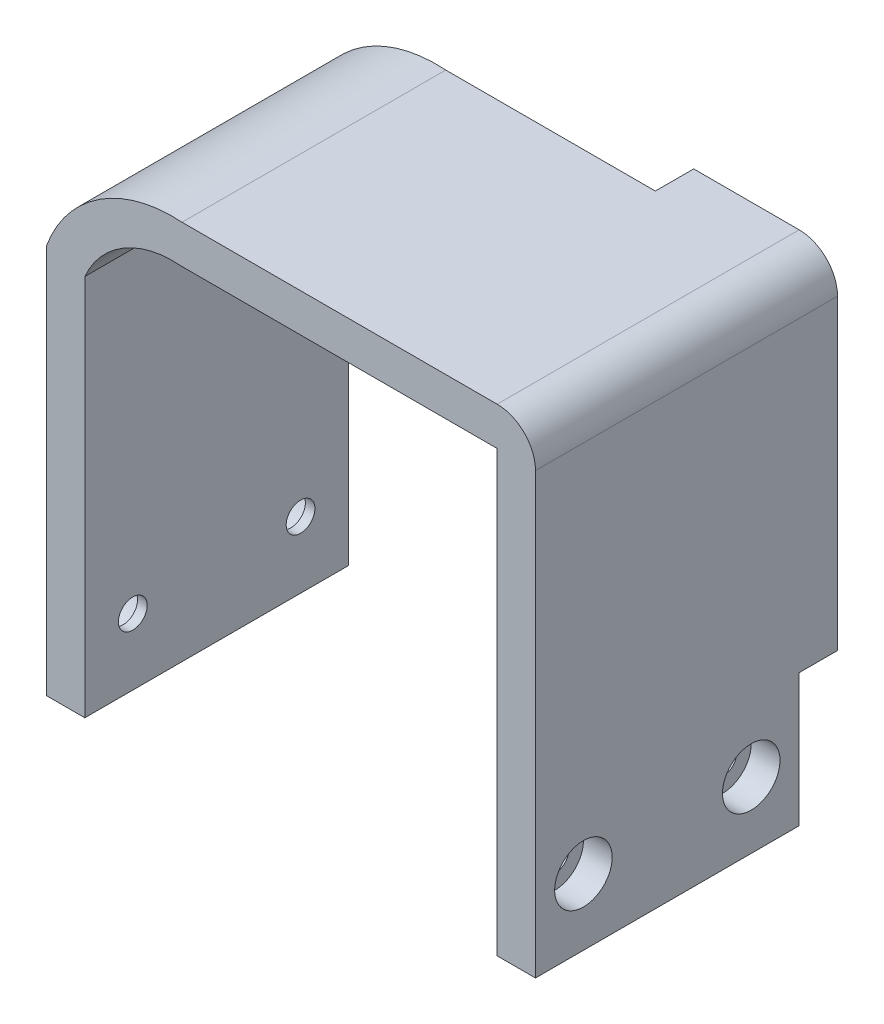
SolidWorks part; units mm, degrees
ref_plane "Front Plane" through (0, 0, 0) normal (0, 0, 1) x (1, 0, 0)
ref_plane "Top Plane" through (0, 0, 0) normal (0, 1, 0) x (1, 0, 0)
ref_plane "Right Plane" through (0, 0, 0) normal (1, 0, 0) x (0, 0, -1)
sketch "Sketch1" plane through (0, 0, 0) normal (0, 0, 1) x (1, 0, 0)
  line L0 (-27.2636, -0.8263) -> (-27.2636, 39.0321)
  line L1 (-17.2741, 45) -> (15.7364, 45)
  line L2 (15.7364, 45) -> (15.7364, -0.8263)
  line L8 (-31.2636, -0.8263) -> (-31.2636, 39.7939)
  line L9 (-17.123, 49) -> (19.7364, 49)
  line L10 (19.7364, 49) -> (19.7364, -0.8263)
  line L11 (-27.2636, -0.8263) -> (-31.2636, -0.8263)
  line L12 (15.7364, -0.8263) -> (19.7364, -0.8263)
  line L13 (15.7364, 18) -> (15.7364, 40) construction
  arc A0 (-27.2636, 39.0321) -> (-17.2741, 45) centre (-18.0976, 35.034) cw
  arc A2 (-31.2636, 39.7939) -> (-17.123, 49) centre (-18.0976, 35.034) cw
  dimension "D2" = 10
  dimension "D1" = 4
extrude "Boss-Extrude1" add sketch "Sketch1" along normal blind 27.5
sketch "Sketch3" plane through (0, 0, 0) normal (0, 0, -1) x (-1, 0, 0)
  line L0 (-15.7364, 13) -> (17.2741, 13) construction
  line L1 (-19.7364, 49) -> (-4.7364, 49)
  line L2 (-19.7364, 49) -> (-19.7364, 13)
  line L3 (-19.7364, 13) -> (-4.7364, 13)
  line L4 (-4.7364, 49) -> (-4.7364, 13)
  dimension "D2" = 15
extrude "Boss-Extrude2" add sketch "Sketch3" along normal blind 4
sketch "Sketch4" plane through (0, 0, 0) normal (0, 0, 1) x (1, 0, 0)
  circle A0 centre (12.7364, 42.5) radius 1.25
  circle A1 centre (12.7364, 42.5) radius 2
  circle A2 centre (12.7364, 15.5) radius 1.25
  circle A3 centre (12.7364, 15.5) radius 2
  dimension "D1" = 2.5
  dimension "D2" = 4
extrude "Cut-Extrude1" cut sketch "Sketch4" against normal through all contours A0 | A2 region at (12.7364, 42.5, 0) region at (12.7364, 15.5, 0)
extrude "Cut-Extrude2" cut sketch "Sketch4<3>" along normal blind 2 from surface starting at face at (13.9864, 42.5, -4)
sketch "Sketch4<3>" plane through (0, 0, 0) normal (0, 0, 1) x (1, 0, 0) same geometry as "Sketch4"
sketch "Sketch5" plane through (19.7364, 0, 0) normal (1, 0, 0) x (0, 0, -1)
  line L0 (0, -0.8263) -> (0, 13) construction
  line L1 (-27.5, -0.8263) -> (-27.5, 49) construction
  circle A0 centre (-5, 6.0869) radius 1.5
  circle A1 centre (-22.5, 6.0869) radius 1.5
  circle A2 centre (-22.5, 6.0869) radius 3
  circle A3 centre (-5, 6.0869) radius 3
  point P6 (0, 6.0869)
  dimension "D1" = 3
  dimension "D4" = 6
  dimension "D2" = 5
  dimension "D3" = 5
extrude "Cut-Extrude3" cut sketch "Sketch5" against normal through all contours A1 | A0 region at (19.7364, 6.0869, 5) region at (19.7364, 6.0869, 22.5)
extrude "Cut-Extrude4" cut sketch "Sketch5<3>" against normal blind 3
sketch "Sketch5<3>" plane through (19.7364, 0, 0) normal (1, 0, 0) x (0, 0, -1) same geometry as "Sketch5"
ref_plane "Plane1" through (-5.7636, 0, 0) normal (1, 0, 0) x (0, 0, -1)
mirror "Mirror1" about plane through (-5.7636, 0, 0) normal (1, 0, 0) of "Cut-Extrude4"
fillet "Fillet1" radius 4 1 edges at (19.7364, 49, 11.75)
